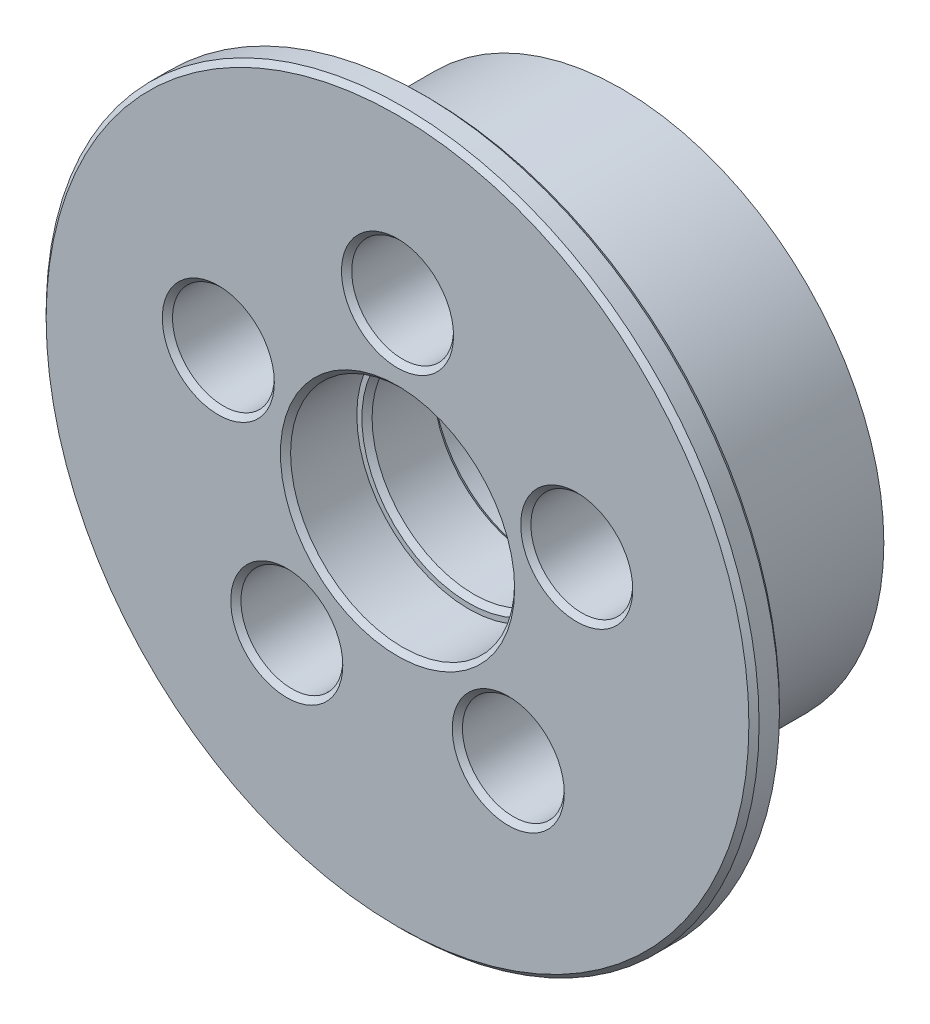
SolidWorks part; units mm, degrees
ref_plane "Front Plane" through (0, 0, 0) normal (0, 0, 1) x (1, 0, 0)
ref_plane "Top Plane" through (0, 0, 0) normal (0, 1, 0) x (1, 0, 0)
ref_plane "Right Plane" through (0, 0, 0) normal (1, 0, 0) x (0, 0, -1)
sketch "Sketch1" plane through (0, 0, 0) normal (0, 0, 1) x (1, 0, 0)
  circle A0 centre (0, 0) radius 25.75
  dimension "D1" = 51.5
extrude "Boss-Extrude1" add sketch "Sketch1" along normal blind 19
sketch "Sketch2" plane through (0, 0, 19) normal (0, 0, 1) x (1, 0, 0)
  circle A0 centre (0, 0) radius 35
  dimension "D1" = 70
extrude "Boss-Extrude2" add sketch "Sketch2" along normal blind 3
sketch "Sketch3" plane through (0, 0, 0) normal (0, 0, -1) x (-1, 0, 0)
  circle A0 centre (0, 0) radius 18.5 construction
  circle A1 centre (0, 18.5) radius 5
  circle A2 centre (17.5945, 5.7168) radius 5
  circle A3 centre (10.874, -14.9668) radius 5
  circle A4 centre (-10.874, -14.9668) radius 5
  circle A5 centre (-17.5945, 5.7168) radius 5
  point P16 (0, 0)
  dimension "D2" = 10
  dimension "D3" = 37
  dimension "D1" = 5
extrude "Cut-Extrude1" cut sketch "Sketch3" against normal through all
sketch "Sketch4" plane through (0, 0, 0) normal (0, 0, -1) x (-1, 0, 0)
  circle A0 centre (0, 0) radius 10
  dimension "D1" = 20
extrude "Cut-Extrude2" cut sketch "Sketch4" against normal through all
sketch "Sketch5" plane through (0, 0, 0) normal (0, 0, -1) x (-1, 0, 0)
  circle A0 centre (0, 0) radius 11
  circle A3 centre (0, 0) radius 10 construction
  dimension "D1" = 1
extrude "Cut-Extrude3" cut sketch "Sketch5" against normal blind 8
sketch "Sketch6" plane through (0, 0, 22) normal (0, 0, 1) x (1, 0, 0)
  circle A0 centre (0, 0) radius 11
  circle A3 centre (0, 0) radius 10 construction
  dimension "D1" = 1
extrude "Cut-Extrude4" cut sketch "Sketch6" against normal blind 7
chamfer "Chamfer1" distance 0.5 angle 45 16 edges at (11, 0, 22) (-15.874, -14.9668, 22) (5.874, -14.9668, 22) (12.5945, 5.7168, 22) (-5, 18.5, 22) (-22.5945, 5.7168, 22) (-11, 0, 0) (-5, 18.5, 0) (-22.5945, 5.7168, 0) (-15.874, -14.9668, 0) (5.874, -14.9668, 0) (12.5945, 5.7168, 0) (-10, 0, 8) (10, 0, 15) (35, 0, 22) (35, 0, 19)
